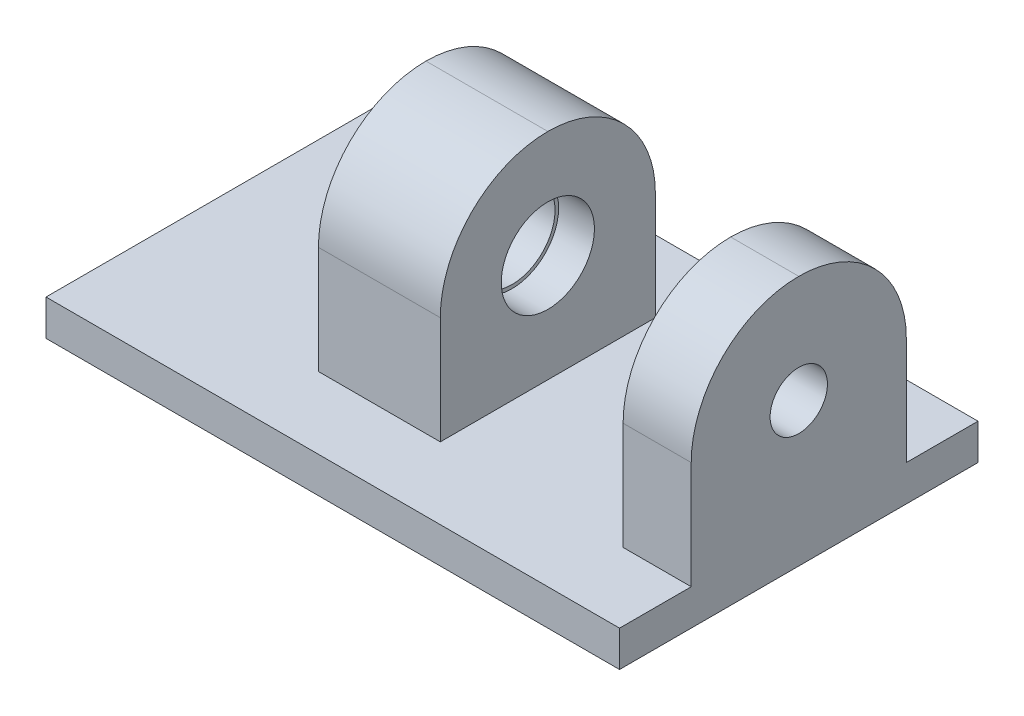
SolidWorks part; units mm, degrees
ref_plane "Front Plane" through (0, 0, 0) normal (0, 0, 1) x (1, 0, 0)
ref_plane "Top Plane" through (0, 0, 0) normal (0, 1, 0) x (1, 0, 0)
ref_plane "Right Plane" through (0, 0, 0) normal (1, 0, 0) x (0, 0, -1)
sketch "Sketch1" plane through (0, 0, 0) normal (0, 1, 0) x (1, 0, 0)
  line L1 (-40, -25) -> (40, -25)
  line L2 (-40, -25) -> (-40, 25)
  line L3 (-40, 25) -> (40, 25)
  line L4 (40, -25) -> (40, 25)
  line L5 (-40, -25) -> (40, 25) construction
  line L6 (-40, 25) -> (40, -25) construction
  point P0 (0, 0)
  dimension "D1" = 80
  dimension "D2" = 50
extrude "Boss-Extrude1" add sketch "Sketch1" along normal blind 5
sketch "Sketch2" plane through (0, 5, 0) normal (0, 1, 0) x (1, 0, 0)
  line L0 (0, 0) -> (40, 0) construction
  line L1 (-12, -15) -> (5, -15)
  line L2 (-12, -15) -> (-12, 15)
  line L3 (-12, 15) -> (5, 15)
  line L4 (5, -15) -> (5, 15)
  line L5 (-12, -15) -> (5, 15) construction
  line L6 (-12, 15) -> (5, -15) construction
  line L7 (30.5, -15) -> (40, -15)
  line L8 (30.5, -15) -> (30.5, 15)
  line L9 (30.5, 15) -> (40, 15)
  line L10 (40, -15) -> (40, 15)
  line L11 (30.5, -15) -> (40, 15) construction
  line L12 (30.5, 15) -> (40, -15) construction
  line L13 (40, -25) -> (40, 25) construction
  point P0 (-3.5, 0)
  point P5 (35.25, 0)
  dimension "D1" = 9.5
  dimension "D2" = 30
  dimension "D3" = 25.5
  dimension "D4" = 30
  dimension "D5" = 17
extrude "Boss-Extrude2" add sketch "Sketch2" along normal blind 30
fillet "Fillet1" radius 15 4 edges at (-3.5, 35, -15) (-3.5, 35, 15) (35.25, 35, -15) (35.25, 35, 15)
sketch "Sketch3" plane through (30.5, 0, 0) normal (-1, 0, 0) x (0, 0, 1)
  circle A0 centre (0, 20) radius 4
  dimension "D1" = 8
extrude "Cut-Extrude1" cut sketch "Sketch3" against normal blind 30
sketch "Sketch4" plane through (5, 0, 0) normal (1, 0, 0) x (0, 0, -1)
  circle A0 centre (0, 20) radius 6.5
  dimension "D1" = 13
extrude "Cut-Extrude2" cut sketch "Sketch4" against normal blind 5
sketch "Sketch5" plane through (-12, 0, 0) normal (-1, 0, 0) x (0, 0, 1)
  circle A0 centre (0, 20) radius 6
  dimension "D1" = 12
extrude "Cut-Extrude3" cut sketch "Sketch5" against normal blind 14
